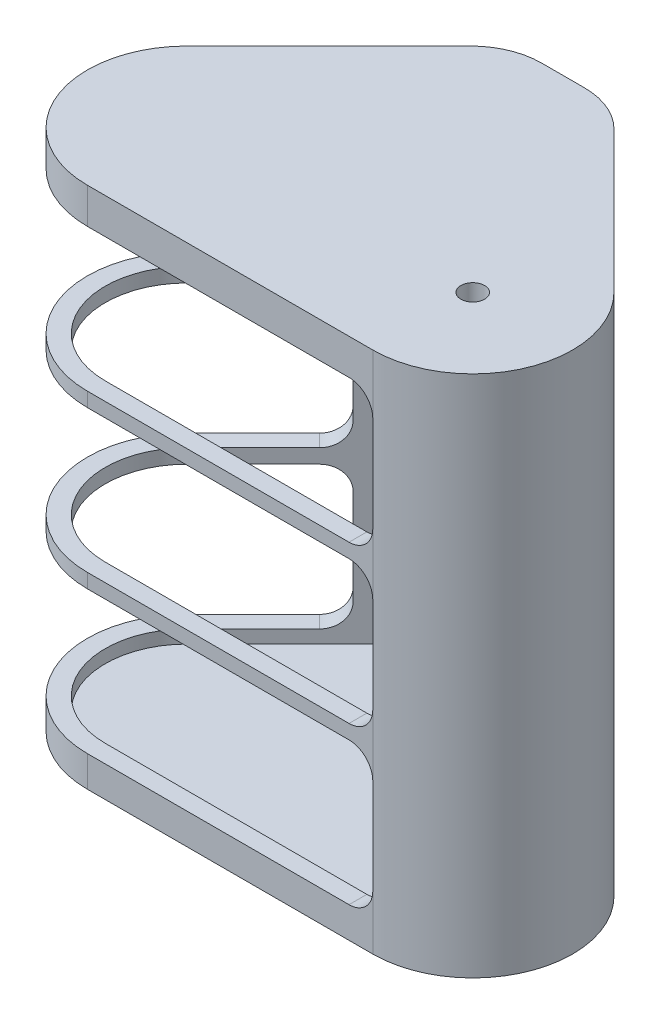
SolidWorks part; units mm, degrees
ref_plane "Front Plane" through (0, 0, 0) normal (0, 0, 1) x (1, 0, 0)
ref_plane "Top Plane" through (0, 0, 0) normal (0, 1, 0) x (1, 0, 0)
ref_plane "Right Plane" through (0, 0, 0) normal (1, 0, 0) x (0, 0, -1)
sketch "Sketch1" plane through (0, 0, 0) normal (0, 1, 0) x (1, 0, 0)
  line L1 (359.2102, 0) -> (0, -359.2102)
  line L2 (359.2102, 0) -> (0, 359.2102)
  line L3 (0, 359.2102) -> (-359.2102, 0)
  line L4 (0, -359.2102) -> (-359.2102, 0)
  line L5 (359.2102, 0) -> (-359.2102, 0) construction
  line L6 (0, 359.2102) -> (0, -359.2102) construction
  point P0 (0, 0)
  dimension "D1" = 508
  dimension "D2" = 508
extrude "Boss-Extrude1" add sketch "Sketch1" along normal blind 558.8
sketch "Sketch2" plane through (0, 558.8, 0) normal (0, 1, 0) x (1, 0, 0)
  line L1 (432.2403, -50.8) -> (-432.2403, -50.8)
  line L2 (432.2403, -50.8) -> (432.2403, 304.8)
  line L3 (432.2403, 304.8) -> (-432.2403, 304.8)
  line L4 (-432.2403, -50.8) -> (-432.2403, 304.8)
  line L5 (432.2403, -50.8) -> (-432.2403, 304.8) construction
  line L6 (432.2403, 304.8) -> (-432.2403, -50.8) construction
  line L7 (616.6138, -508) -> (-616.6138, -508)
  line L8 (616.6138, -508) -> (616.6138, 762)
  line L9 (616.6138, 762) -> (-616.6138, 762)
  line L10 (-616.6138, -508) -> (-616.6138, 762)
  line L11 (616.6138, -508) -> (-616.6138, 762) construction
  line L12 (616.6138, 762) -> (-616.6138, -508) construction
  point P0 (0, 127)
  point P5 (0, 127)
  dimension "D1" = 127
  dimension "D2" = 355.6
  dimension "D3" = 1270
extrude "Cut-Extrude1" cut sketch "Sketch2" against normal through all
fillet "Fillet1" radius 213.36 2 edges at (359.2102, 279.4, 0) (-359.2102, 279.4, 0)
fillet "Fillet2" radius 76.2 2 edges at (54.4102, 279.4, -304.8) (-54.4102, 279.4, -304.8)
sketch "Sketch3" plane through (0, 0, 50.8) normal (0, 0, 1) x (1, 0, 0)
  line L0 (-308.4102, 0) -> (308.4102, 0) construction
  point P2 (0, 0)
  line B0 (-133.35, 503.9843) -> (133.35, 503.9843)
  line B1 (-133.35, 503.9843) -> (-133.35, 376.9843)
  line B2 (-133.35, 376.9843) -> (133.35, 376.9843)
  line B3 (133.35, 503.9843) -> (133.35, 376.9843)
  circle B4 centre (0, 182.1752) radius 139.065
  dimension "D1" = 0
sketch_block_instance "baffle sketch-1"
sketch_block "baffle sketch"
sketch "Sketch4" plane through (0, 0, 50.8) normal (0, 0, 1) x (1, 0, 0)
  line L0 (133.35, 503.9843) -> (-323.85, 503.9843)
  line L1 (133.35, 376.9843) -> (-323.85, 376.9843)
  line L2 (-323.85, 376.9843) -> (-323.85, 503.9843)
  arc A0 (133.35, 376.9843) -> (133.35, 503.9843) centre (91.2289, 440.4843) ccw
  dimension "D1" = 152.4
  dimension "D2" = 457.2
sketch "Sketch7" plane through (0, 0, 0) normal (1, 0, 0) x (0, 0, -1)
  line L0 (-50.8, 503.9843) -> (-50.8, 376.9843) construction
  line L1 (-50.8, 520.7) -> (-30.48, 520.7)
  line L2 (-50.8, 520.7) -> (-50.8, 368.3)
  line L3 (-50.8, 368.3) -> (-30.48, 368.3)
  line L4 (-30.48, 520.7) -> (-30.48, 368.3)
  line L5 (112.9052, 558.8) -> (-50.8, 558.8) construction
  dimension "D1" = 152.4
  dimension "D2" = 38.1
  dimension "D3" = 20.32
fillet "Fillet5" radius 106.68 2 edges at (308.4102, 279.4, 50.8) (-308.4102, 279.4, 50.8)
sketch "Sketch8" plane through (0, 558.8, 0) normal (0, 1, 0) x (1, 0, 0)
  line L0 (0, -50.8) -> (-152.4619, -50.8)
  line L1 (-152.4619, -50.8) -> (152.4619, -50.8) construction
  line L2 (-227.8961, 131.3142) -> (-139.3068, 219.9035)
  line L4 (-76.7287, 282.4815) -> (-227.8961, 131.3142) construction
  arc A0 (-227.8961, 131.3142) -> (-152.4619, -50.8) centre (-152.4619, 55.88) ccw
shell "Shell1" thickness 19.05
sweep "Cut-Sweep1" cut profiles "Sketch7" path "Sketch8"
extrude "Cut-Extrude2" cut sketch "Sketch7<2>" along normal blind 152.4
sketch "Sketch7<2>" plane through (0, 0, 0) normal (1, 0, 0) x (0, 0, -1) same geometry as "Sketch7"
fillet "Fillet6" radius 25.4 4 edges at (152.4, 368.3, 41.275) (152.4, 520.7, 41.275) (-132.5716, 520.7, -213.1683) (-132.5716, 368.3, -213.1683)
pattern_linear "LPattern1" count 3 spacing 167.64 along (0, -1, 0) of "Cut-Extrude2", "Fillet6", "Cut-Sweep1"
sketch "Sketch9" plane through (0, 19.05, 0) normal (0, 1, 0) x (1, 0, 0)
  line L0 (22.8472, 285.75) -> (-22.8472, 285.75)
  line L2 (-63.2583, 269.0112) -> (-214.4257, 117.8438)
  line L4 (214.4257, 117.8438) -> (63.2583, 269.0112)
  line L6 (-152.4619, -31.75) -> (152.4619, -31.75)
  arc A0 (-22.8472, 285.75) -> (-63.2583, 269.0112) centre (-22.8472, 228.6) ccw
  arc A2 (63.2583, 269.0112) -> (22.8472, 285.75) centre (22.8472, 228.6) ccw
  arc A4 (152.4619, -31.75) -> (214.4257, 117.8438) centre (152.4619, 55.88) ccw
  arc A6 (-214.4257, 117.8438) -> (-152.4619, -31.75) centre (-152.4619, 55.88) ccw
  line B0 (22.8472, 285.75) -> (-22.8472, 285.75)
  line B1 (-63.2583, 269.0112) -> (-214.4257, 117.8438)
  line B2 (214.4257, 117.8438) -> (63.2583, 269.0112)
  line B3 (-152.4619, -31.75) -> (152.4619, -31.75)
  arc B4 (-22.8472, 285.75) -> (-63.2583, 269.0112) centre (-22.8472, 228.6) ccw
  arc B5 (63.2583, 269.0112) -> (22.8472, 285.75) centre (22.8472, 228.6) ccw
  arc B6 (152.4619, -31.75) -> (214.4257, 117.8438) centre (152.4619, 55.88) ccw
  arc B7 (-214.4257, 117.8438) -> (-152.4619, -31.75) centre (-152.4619, 55.88) ccw
sketch_block_instance "Block1-1"
sketch_block "Block1"
sketch "Sketch10" plane through (0, 558.8, 0) normal (0, 1, 0) x (1, 0, 0)
  circle A1 centre (152.4619, 55.88) radius 12.7
  dimension "D1" = 25.4
extrude "Cut-Extrude3" cut sketch "Sketch10" against normal through all
